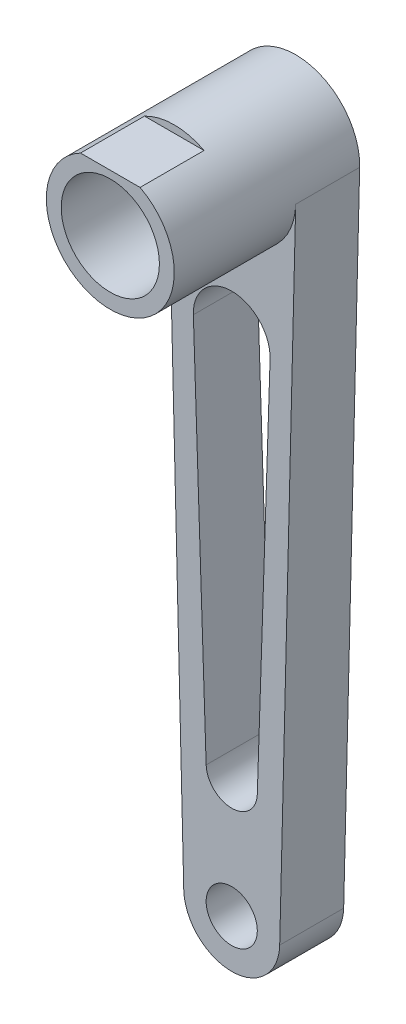
SolidWorks part; units mm, degrees
material "PEI"
ref_plane "Front Plane" through (0, 0, 0) normal (0, 0, 1) x (1, 0, 0)
ref_plane "Top Plane" through (0, 0, 0) normal (0, 1, 0) x (1, 0, 0)
ref_plane "Right Plane" through (0, 0, 0) normal (1, 0, 0) x (0, 0, -1)
sketch "Sketch1" plane through (0, 0, 0) normal (0, 0, 1) x (1, 0, 0)
  line L0 (-10.294, 11.8201) -> (-7.347, -107.9077)
  line L1 (0, -101.6) -> (0, 0) construction
  line L2 (7.347, -107.9067) -> (10.2653, 10.6574)
  line L3 (6.244, -15.7837) -> (3.867, -87.0546)
  line L4 (-6.2592, -15.3276) -> (-3.8401, -87.8596)
  circle A0 centre (0, 0) radius 10
  circle A1 centre (0, 0) radius 7.675
  circle A2 centre (0, -101.6) radius 7.5
  circle A3 centre (0, -101.6) radius 4
  circle A6 centre (0, -23) radius 6
  circle A7 centre (0, -83) radius 4
  dimension "D1" = 15.35
  dimension "D2" = 20
  dimension "D3" = 15
  dimension "D5" = 8
  dimension "D7" = 12
  dimension "D8" = 60
  dimension "D9" = 23
  dimension "D6" = 8
  dimension "D4" = 101.6
extrude "Boss-Extrude2" add sketch "Sketch1" along normal blind 10 contours L1 A2 L2 A0 | A2 L1 A0 L0 | A3 A2 region at (0, -11.0349, 0) region at (-0.0897, -94.3127, 0)
extrude "Boss-Extrude3" add sketch "Sketch1<6>" along normal blind 28.98 contours A0 A1 region at (-0.1196, 9.7164, 0)
sketch "Sketch1<6>" plane through (0, 0, 0) normal (0, 0, 1) x (1, 0, 0) same geometry as "Sketch1"
sketch "Sketch2" plane through (0, 0, 28.98) normal (0, 0, 1) x (1, 0, 0)
  line L0 (-10.0333, 8.85) -> (9.9921, 8.85)
  line L1 (9.9921, 8.85) -> (9.9921, 18.6582)
  line L2 (9.9921, 18.6582) -> (-10.0333, 18.6582)
  line L3 (-10.0333, 18.6582) -> (-10.0333, 8.85)
  circle A0 centre (0, 0) radius 10 construction
  point P0 (9.9921, 18.6903)
  point P3 (-0.0206, 8.85)
  dimension "D1" = 8.85
extrude "Cut-Extrude1" cut sketch "Sketch2" against normal blind 10
